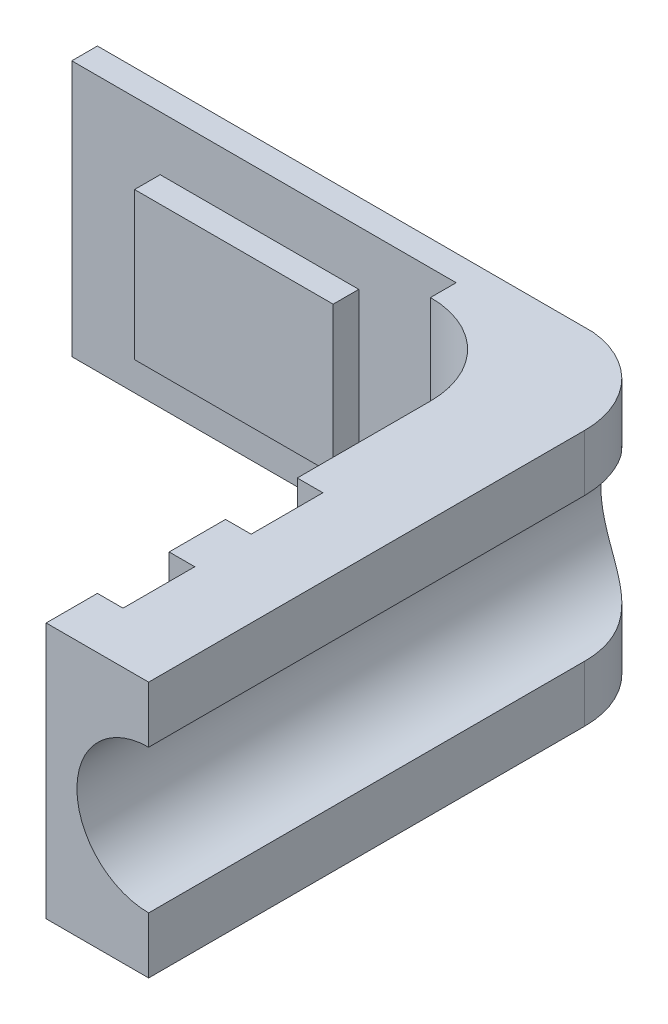
SolidWorks part; units mm, degrees
ref_plane "Front Plane" through (0, 0, 0) normal (0, 0, 1) x (1, 0, 0)
ref_plane "Top Plane" through (0, 0, 0) normal (0, 1, 0) x (1, 0, 0)
ref_plane "Right Plane" through (0, 0, 0) normal (1, 0, 0) x (0, 0, -1)
sketch "Sketch1" plane through (0, 0, 0) normal (0, 1, 0) x (1, 0, 0)
  line L0 (-15, 4.5) -> (0, 4.5)
  line L2 (-15, 4.5) -> (-15, 5.5)
  line L3 (-15, 5.5) -> (4.3465, 5.5)
  line L6 (3.5, 0) -> (3.5, -15)
  line L7 (3.5, -15) -> (7.5, -15)
  line L8 (7.5, 2.0172) -> (7.5, -15)
  line L9 (0, 4.5) -> (0, 3.5)
  arc A1 (0, 3.5) -> (3.5, 0) centre (0, 0) cw
  arc A4 (7.5, 2.0172) -> (4.3465, 5.5) centre (4, 2.0172) ccw
  point P0 (0, 0)
  dimension "D2" = 15
  dimension "D5" = 3.5
  dimension "D6" = 3.5
  dimension "D9" = 2.0172
  dimension "D1" = 1
  dimension "D3" = 15
  dimension "D4" = 4
  dimension "D7" = 2
  dimension "D8" = 19.3465
extrude "Boss-Extrude1" add sketch "Sketch1" along normal blind 10
sketch "Sketch2" plane through (0, 0, -4.5) normal (0, 0, 1) x (1, 0, 0)
  line L0 (0, 10) -> (0, 0) construction
  line L1 (-11.55, 7.875) -> (-3.8, 7.875)
  line L2 (-11.55, 7.875) -> (-11.55, 2.125)
  line L3 (-11.55, 2.125) -> (-3.8, 2.125)
  line L4 (-3.8, 7.875) -> (-3.8, 2.125)
  line L5 (-11.55, 7.875) -> (-3.8, 2.125) construction
  line L6 (-11.55, 2.125) -> (-3.8, 7.875) construction
  line L7 (-15, 10) -> (0, 10) construction
  point P0 (-7.675, 5)
  point P10 (0, 0)
  dimension "D1" = 7.75
  dimension "D2" = 5.75
  dimension "D3" = 3.8
  dimension "D4" = 2.125
extrude "Boss-Extrude2" add sketch "Sketch2" along normal blind 1
sketch "Sketch3" plane through (0, 0, 15) normal (0, 0, 1) x (1, 0, 0)
  line L0 (7.5, 10) -> (7.5, 0) construction
  line L1 (7.5, 7.8) -> (7.5, 2.2)
  arc A0 (7.5, 7.8) -> (7.5, 2.2) centre (7.5, 5) ccw
  dimension "D1" = 5.6
extrude "Cut-Extrude1" cut sketch "Sketch3" against normal through all
sketch "Sketch4" plane through (0, 0, 15) normal (0, 0, 1) x (1, 0, 0)
  line L1 (3.5, 10) -> (7.5, 10) construction
  line L6 (4.5, 10) -> (3.5, 9)
  line L7 (3.5, 10) -> (3.5, 0) construction
  line L8 (3.5, 9) -> (3.5, 10)
  line L9 (3.5, 10) -> (4.5, 10)
  line L10 (3.5, 1) -> (3.5, 0)
  line L11 (3.5, 0) -> (4.5, 0)
  line L12 (3.5, 0) -> (7.5, 0) construction
  line L13 (4.5, 0) -> (3.5, 1)
  dimension "D1" = 1
  dimension "D2" = 1
  dimension "D3" = 1
  dimension "D4" = 1
extrude "Cut-Extrude2" cut sketch "Sketch4" against normal blind 2.8 from offset 2 offset against normal yes
extrude "Cut-Extrude3" cut sketch "Sketch4<2>" against normal blind 2.8 from offset 7 offset against normal yes
sketch "Sketch4<2>" plane through (0, 0, 15) normal (0, 0, 1) x (1, 0, 0) same geometry as "Sketch4"
